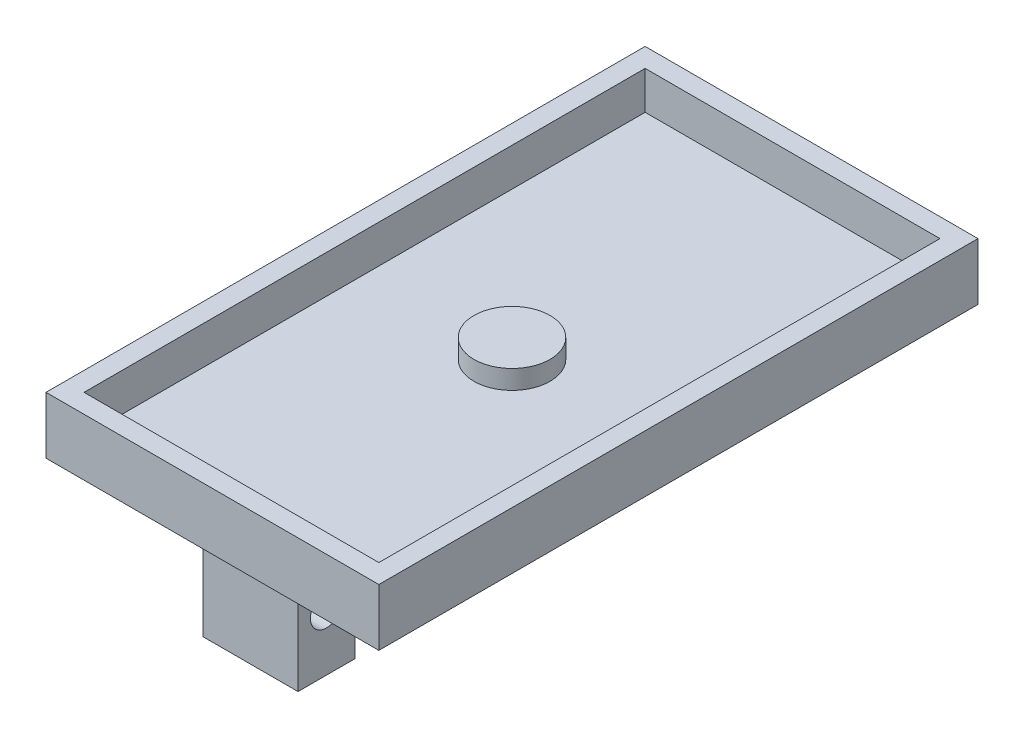
SolidWorks part; units mm, degrees
ref_plane "Front Plane" through (0, 0, 0) normal (0, 0, 1) x (1, 0, 0)
ref_plane "Top Plane" through (0, 0, 0) normal (0, 1, 0) x (1, 0, 0)
ref_plane "Right Plane" through (0, 0, 0) normal (1, 0, 0) x (0, 0, -1)
sketch "Sketch1" plane through (0, 0, 0) normal (0, 1, 0) x (1, 0, 0)
  line L1 (-17.5, 31.5) -> (17.5, 31.5)
  line L2 (-17.5, 31.5) -> (-17.5, -31.5)
  line L3 (-17.5, -31.5) -> (17.5, -31.5)
  line L4 (17.5, 31.5) -> (17.5, -31.5)
  line L5 (-17.5, 31.5) -> (17.5, -31.5) construction
  line L6 (-17.5, -31.5) -> (17.5, 31.5) construction
  point P0 (0, 0)
  dimension "D1" = 35
  dimension "D2" = 63
extrude "Boss-Extrude1" add sketch "Sketch1" along normal blind 2
sketch "Sketch2" plane through (0, 0, 0) normal (0, -1, 0) x (1, 0, 0)
  line L1 (-5, 21.5) -> (5, 21.5)
  line L5 (-5, 21.5) -> (5, -1.5) construction
  line L6 (-5, -1.5) -> (5, 21.5) construction
  line L7 (5, 21.5) -> (-5, 21.5)
  line L8 (5, 21.5) -> (5, 27.5)
  line L9 (5, 27.5) -> (-5, 27.5)
  line L10 (-5, 21.5) -> (-5, 27.5)
  line L11 (0, 10) -> (8.9623, 10) construction
  line L12 (5, -7.5) -> (-5, -7.5)
  line L13 (-5, -1.5) -> (-5, -7.5)
  line L14 (-5, -1.5) -> (5, -1.5)
  line L15 (5, -1.5) -> (5, -7.5)
  line L17 (-17.5, 31.5) -> (17.5, 31.5) construction
  point P0 (0, 10)
  line M14 (17.5, 31.5) -> (-17.5, 31.5)
  dimension "D1" = 10
  dimension "D2" = 23
  dimension "D3" = 6
  dimension "D4" = 10
extrude "Boss-Extrude2" add sketch "Sketch2" along normal blind 12 contours L10 L1 L8 M14 | L15 L14 L13 L12 region at (0, 0, 24.5) region at (0, 0, -4.5)
sketch "Sketch3" plane through (5, 0, 0) normal (1, 0, 0) x (0, 0, -1)
  line L0 (4.5, -12) -> (4.5, 0) construction
  line L1 (7.5, -6) -> (1.5, -6) construction
  line L2 (-21.5, -12) -> (-27.5, -12) construction
  line L4 (7.5, 0) -> (1.5, 0)
  line L5 (1.5, 0) -> (1.5, -12)
  line L6 (1.5, -12) -> (7.5, -12)
  line L7 (7.5, -12) -> (7.5, 0)
  line L8 (7.5, 0) -> (1.5, 0) construction
  line L9 (1.5, 0) -> (1.5, -12) construction
  line L10 (1.5, -12) -> (7.5, -12) construction
  line L11 (7.5, -12) -> (7.5, 0) construction
  circle A0 centre (4.5, -6) radius 1.7
  circle A1 centre (-24.5, -6) radius 1.7
  point P11 (4.5, -6)
  point P15 (-24.5, -12)
  dimension "D2" = 3.4
  dimension "D1" = 0
extrude "Cut-Extrude1" cut sketch "Sketch3" against normal up to surface (10 mm away) up to face at (-5, -6, -4.5)
fillet "Fillet1" radius 4 2 edges at (0, 0, -7.5) (0, 0, 27.5)
sketch "Sketch4" plane through (0, 2, 0) normal (0, 1, 0) x (1, 0, 0)
  line L8 (15.5, -29.5) -> (15.5, 29.5)
  line L9 (15.5, 29.5) -> (-15.5, 29.5)
  line L10 (-15.5, 29.5) -> (-15.5, -29.5)
  line L11 (-15.5, -29.5) -> (15.5, -29.5)
  line L12 (15.5, -29.5) -> (15.5, 29.5)
  line L13 (15.5, 29.5) -> (-15.5, 29.5)
  line L14 (-15.5, 29.5) -> (-15.5, -29.5)
  line L15 (-15.5, -29.5) -> (15.5, -29.5)
  line L16 (17.5, -31.5) -> (17.5, 31.5)
  line L17 (17.5, 31.5) -> (-17.5, 31.5)
  line L18 (-17.5, 31.5) -> (-17.5, -31.5)
  line L19 (-17.5, -31.5) -> (17.5, -31.5)
  line L20 (17.5, -31.5) -> (17.5, 31.5)
  line L21 (17.5, 31.5) -> (-17.5, 31.5)
  line L22 (-17.5, 31.5) -> (-17.5, -31.5)
  line L23 (-17.5, -31.5) -> (17.5, -31.5)
  line M9 (17.5, -31.5) -> (17.5, 31.5)
  line M10 (17.5, 31.5) -> (-17.5, 31.5)
  line M11 (-17.5, 31.5) -> (-17.5, -31.5)
  line M12 (-17.5, -31.5) -> (17.5, -31.5)
  dimension "D1" = 2
  dimension "D2" = 0
extrude "Boss-Extrude4" add sketch "Sketch4" along normal blind 4 contours L15 L14 L13 L12 M12 M9 M10 M11 region at (0, 2, 30.7793)
sketch "Sketch5" plane through (0, 2, 0) normal (0, 1, 0) x (1, 0, 0)
  circle A0 centre (0, 0) radius 4
  dimension "D1" = 8
extrude "Boss-Extrude5" add sketch "Sketch5" along normal blind 2
